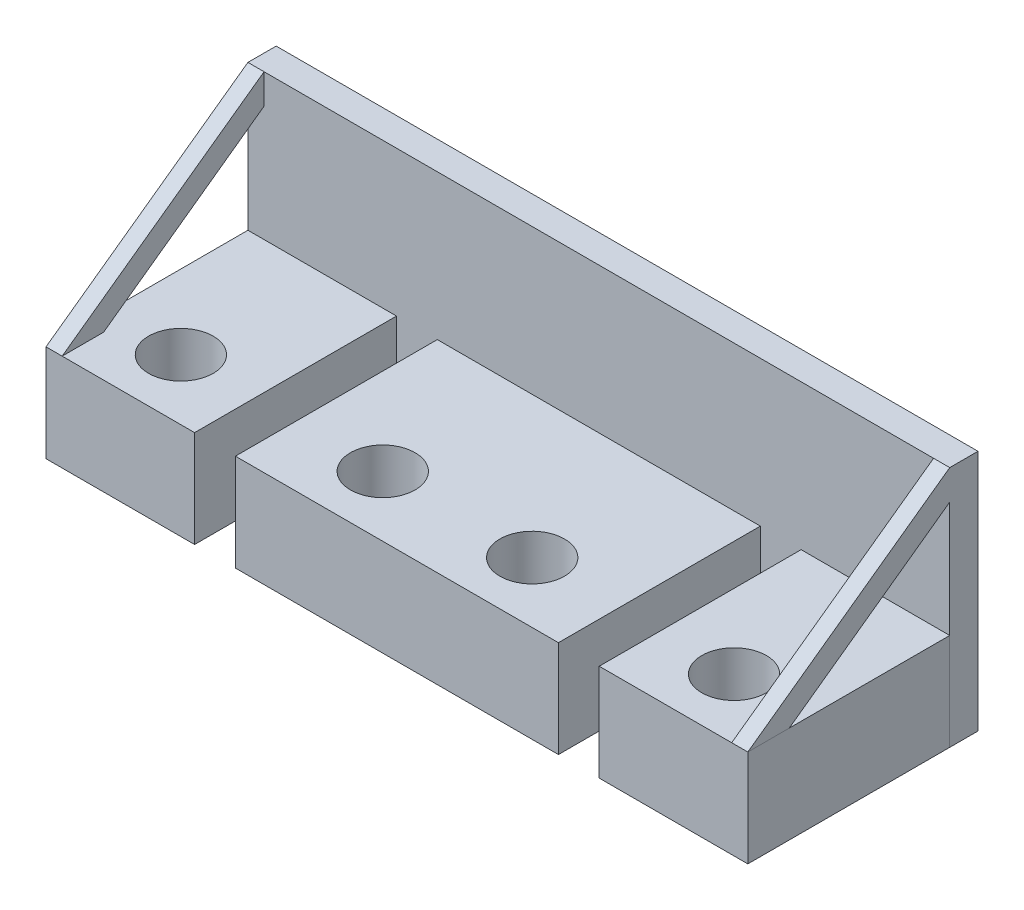
SolidWorks part; units mm, degrees
ref_plane "Front Plane" through (0, 0, 0) normal (0, 0, 1) x (1, 0, 0)
ref_plane "Top Plane" through (0, 0, 0) normal (0, 1, 0) x (1, 0, 0)
ref_plane "Right Plane" through (0, 0, 0) normal (1, 0, 0) x (0, 0, -1)
sketch "Sketch1" plane through (0, 0, 0) normal (0, 1, 0) x (1, 0, 0)
  line L0 (20, 0) -> (20, 25) construction
  line L1 (0, 0) -> (40, 0)
  line L2 (0, 0) -> (0, 25)
  line L3 (0, 25) -> (40, 25)
  line L4 (40, 0) -> (40, 25)
  line L5 (10.75, 7.5) -> (10.75, 0) construction
  line L6 (20, 0) -> (-14.25, 0) construction
  line L15 (0, 7.5) -> (-5.05, 7.5) construction
  line L16 (-14.25, 0) -> (-14.25, 7.5) construction
  line L17 (-23.45, 25) -> (-5.05, 25)
  line L18 (-23.45, 25) -> (-23.45, 0)
  line L19 (-23.45, 0) -> (-5.05, 0)
  line L20 (-5.05, 25) -> (-5.05, 0)
  line L24 (63.45, 0) -> (45.05, 0)
  line L25 (45.05, 25) -> (45.05, 0)
  line L26 (63.45, 25) -> (45.05, 25)
  line L27 (63.45, 25) -> (63.45, 0)
  circle A0 centre (10.75, 7.5) radius 4
  circle A4 centre (-14.25, 7.5) radius 4
  circle A5 centre (54.25, 7.5) radius 4
  circle A6 centre (29.25, 7.5) radius 4
  point P5 (-20.8202, 0)
  point P10 (0, 0)
  dimension "D4" = 8
  dimension "D1" = 40
  dimension "D2" = 25
  dimension "D3" = 9.25
  dimension "D5" = 34.25
  dimension "D6" = 5.05
  dimension "D7" = 7.5
extrude "Boss-Extrude1" add sketch "Sketch1" along normal blind 12
ref_plane "Plane1" through (20, 0, 0) normal (-1, 0, 0) x (0, 0, 1)
sketch "Sketch2" plane through (20, 0, 0) normal (-1, 0, 0) x (0, 0, 1)
  line L1 (-25, 0) -> (-28.5, 0)
  line L2 (-25, 0) -> (-25, 30)
  line L3 (-25, 30) -> (-28.5, 30)
  line L4 (-28.5, 0) -> (-28.5, 30)
  dimension "D1" = 3.5
  dimension "D2" = 30
extrude "Boss-Extrude2" add sketch "Sketch2" along normal up to surface (43.45 mm away) and the other way up to surface (43.45 mm away) up to face at (-23.45, 6, -12.5) other way up to face at (63.45, 6, -12.5)
sketch "Sketch3" plane through (-23.45, 0, 0) normal (-1, 0, 0) x (0, 0, 1)
  line L0 (0, 12) -> (-25, 30)
  line L1 (-25, 30) -> (-25, 26.3033)
  line L2 (-25, 30) -> (-25, 0) construction
  line L3 (-25, 26.3033) -> (-5.1343, 12)
  line L4 (-25, 12) -> (0, 12) construction
  line L5 (-5.1343, 12) -> (0, 12)
  line L6 (-15.0672, 19.1516) -> (-13.3142, 21.5863) construction
  dimension "D1" = 3
extrude "Boss-Extrude3" add sketch "Sketch3" against normal blind 2
mirror "Mirror1" about plane through (20, 0, 0) normal (-1, 0, 0) of "Boss-Extrude3"
equation "\"verticalSlideWidth\"=14.45"
